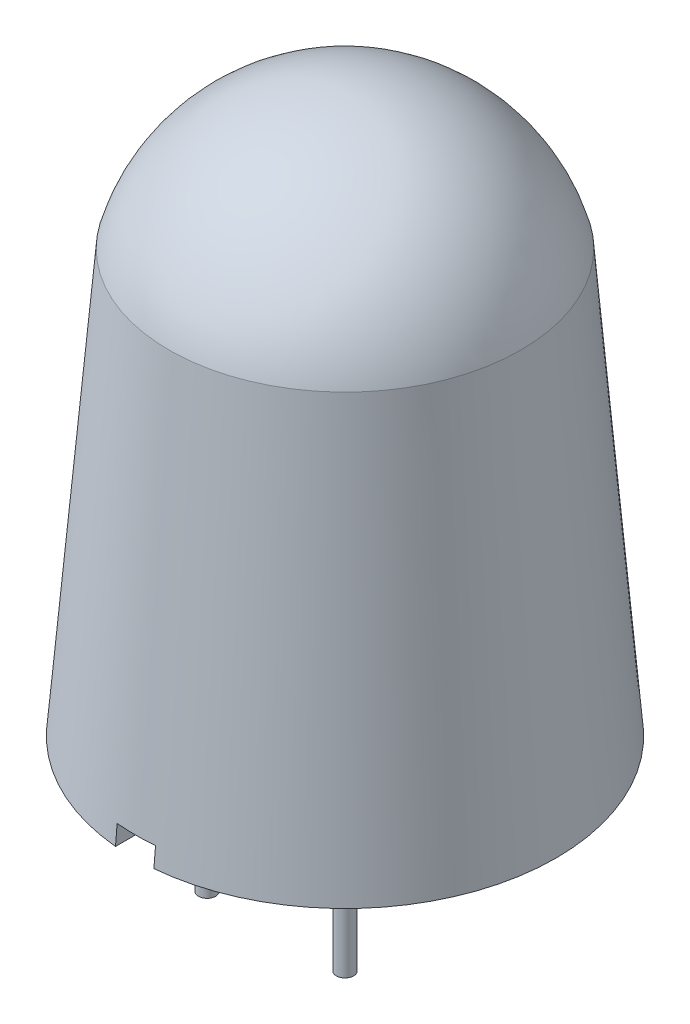
SolidWorks part; units mm, degrees
ref_plane "Front Plane" through (0, 0, 0) normal (0, 0, 1) x (1, 0, 0)
ref_plane "Top Plane" through (0, 0, 0) normal (0, 1, 0) x (1, 0, 0)
ref_plane "Right Plane" through (0, 0, 0) normal (1, 0, 0) x (0, 0, -1)
sketch "Sketch1" plane through (0, 0, 0) normal (0, 0, 1) x (1, 0, 0)
  line L0 (0, 0) -> (5.5, 0)
  line L1 (0, 0) -> (0, 38.9037) construction
  line L2 (0, 0) -> (0, 14.5)
  line L3 (5.5, 0) -> (4.5826, 11)
  arc A0 (0, 14.5) -> (4.5826, 11) centre (0, 9.75) cw
  dimension "D3" = 4.75
  dimension "D1" = 5.5
  dimension "D2" = 14.5
  dimension "D4" = 11
revolve "Revolve1" add sketch "Sketch1" angle 360 about L1
sketch "Sketch2" plane through (0, 0, 0) normal (0, -1, 0) x (1, 0, 0)
  circle A0 centre (0, 0) radius 5
  dimension "D1" = 10
extrude "Cut-Extrude1" cut sketch "Sketch2" against normal blind 1
sketch "Sketch3" plane through (0, 0, 0) normal (0, 0, 1) x (1, 0, 0)
  line L0 (0.5, -0.5) -> (-0.5, 0.5) construction
  line L1 (-0.5, -0.5) -> (0.5, -0.5)
  line L2 (-0.5, -0.5) -> (-0.5, 0.5)
  line L3 (-0.5, 0.5) -> (0.5, 0.5)
  line L4 (0.5, -0.5) -> (0.5, 0.5)
  line L5 (0.5, 0.5) -> (-0.5, -0.5) construction
  dimension "D1" = 1
  dimension "D2" = 1
extrude "Cut-Extrude2" cut sketch "Sketch3" against normal through all and the other way blind 12
sketch "Sketch4" plane through (0, 1, 0) normal (0, -1, 0) x (1, 0, 0)
  line L0 (0, 0) -> (1.7961, 1.7961) construction
  line L1 (0, 0) -> (-1.7961, 1.7961) construction
  line L2 (0, 0) -> (-1.7961, -1.7961) construction
  line L3 (0, 0) -> (-7.8858, 0) construction
  circle A0 centre (0, 0) radius 2.54 construction
  circle A1 centre (1.7961, 1.7961) radius 0.225
  circle A2 centre (-1.7961, 1.7961) radius 0.225
  circle A3 centre (-1.7961, -1.7961) radius 0.225
  dimension "D1" = 5.08
  dimension "D5" = 0.45
  dimension "D2" = 135
  dimension "D3" = 45
  dimension "D4" = 90
extrude "Boss-Extrude1" add sketch "Sketch4" along normal blind 4.5
